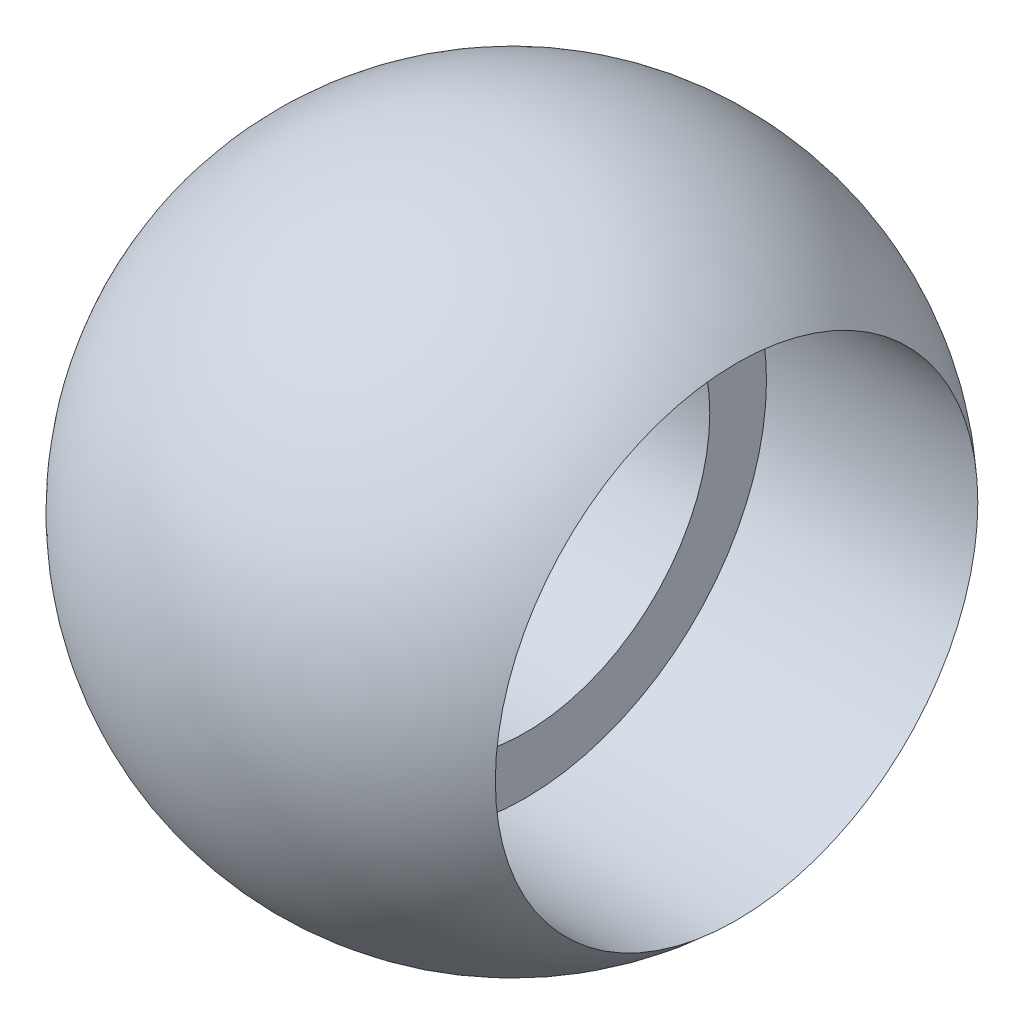
SolidWorks part; units mm, degrees
ref_plane "Front Plane" through (0, 0, 0) normal (0, 0, 1) x (1, 0, 0)
ref_plane "Top Plane" through (0, 0, 0) normal (0, 1, 0) x (1, 0, 0)
ref_plane "Right Plane" through (0, 0, 0) normal (1, 0, 0) x (0, 0, -1)
sketch "Sketch1" plane through (0, 0, 0) normal (0, 1, 0) x (1, 0, 0)
  line L1 (0, 3.175) -> (0, -3.175)
  arc A0 (0, -3.175) -> (0, 3.175) centre (0, 0) ccw
  dimension "D1" = 6.35
revolve "Revolve3" add sketch "Sketch1" angle 360 about L1
ref_point "Point1"
ref_plane "Plane1" through (3.175, 0, 0) normal (1, 0, 0) x (0, 0, -1)
sketch "Sketch2" plane through (3.175, 0, 0) normal (1, 0, 0) x (0, 0, -1)
  circle A0 centre (0, 0) radius 1.778
extrude "Cut-Extrude1" cut sketch "Sketch2" against normal through all
sketch "Sketch3" plane through (3.175, 0, 0) normal (1, 0, 0) x (0, 0, -1)
  circle A0 centre (0, 0) radius 2.3241
  dimension "D1" = 4.6482
extrude "Cut-Extrude2" cut sketch "Sketch3" against normal blind 3.048
ref_axis "Axis1" through (-2.6305, 0, 0) along (1, 0, 0)
ref_plane "Plane3" through (0.127, 0, 0) normal (1, 0, 0) x (0, 0, -1)
sketch "Sketch4" plane through (0.127, 0, 0) normal (1, 0, 0) x (0, 0, -1)
  line L0 (0, 0) -> (-3.175, 0)
  circle A0 centre (0, 0) radius 3.175 construction
ref_plane "Plane4" through (0, 0, 0) normal (0, -1, 0) x (-1, 0, 0)
sketch "Sketch5" plane through (0, 0, 0) normal (0, -1, 0) x (-1, 0, 0)
  line L0 (-2.1631, 2.3241) -> (-2.1631, -2.3241)
  line L1 (-2.1631, -2.3241) -> (-2.1631, 2.3241) construction
  line L2 (-2.1631, -2.3241) -> (-0.127, -2.3241)
  line L3 (-0.127, 0) -> (-0.127, -3.175) construction
  line L4 (-0.127, -2.3241) -> (-0.127, 2.3241)
  line L5 (-0.127, 2.5565) -> (-0.127, -2.5565) construction
  line L6 (-0.127, 2.3241) -> (-2.1631, 2.3241)
  line L7 (2.6305, -1.778) -> (-0.127, -1.778)
  line L8 (2.6305, 1.778) -> (2.6305, -1.778) construction
  line L9 (-0.127, 0) -> (2.6305, 0)
  line L10 (2.6305, 0) -> (-0.127, 0) construction
  line L11 (-0.127, -2.3241) -> (-2.1631, -2.3241)
  arc A0 (-2.1631, -2.3241) -> (2.6305, -1.778) centre (-0.0048, 0.0422) ccw
  arc A1 (-2.1631, 2.3241) -> (2.6305, 1.778) centre (-0.0048, -0.0422) cw
